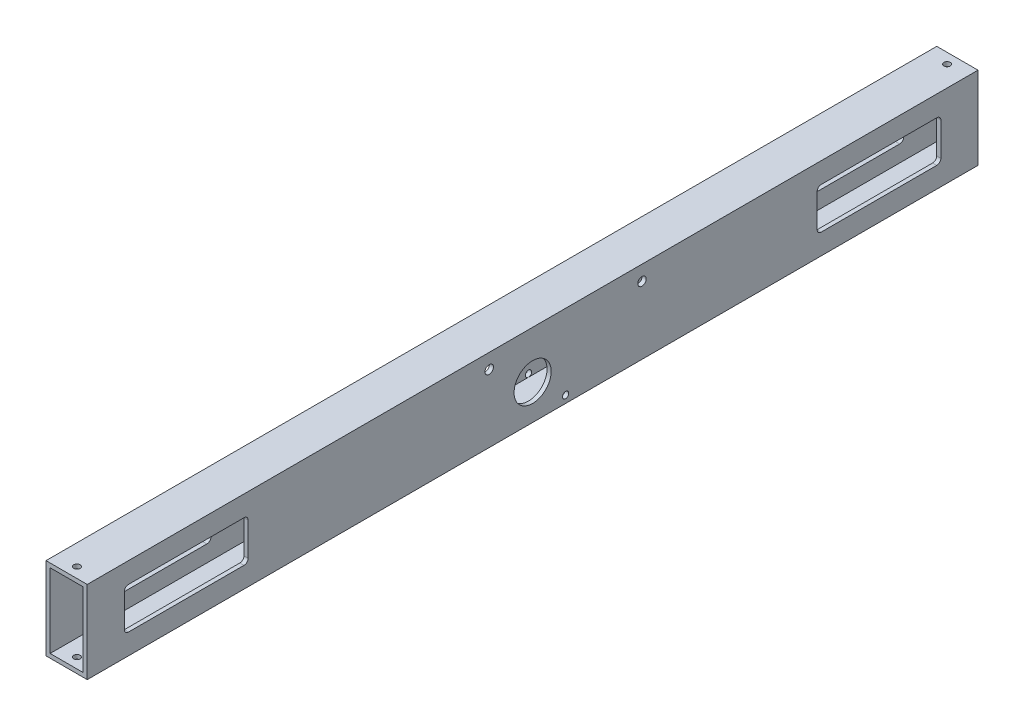
SolidWorks part; units mm, degrees
ref_plane "Front Plane" through (0, 0, 0) normal (0, 0, 1) x (1, 0, 0)
ref_plane "Top Plane" through (0, 0, 0) normal (0, 1, 0) x (1, 0, 0)
ref_plane "Right Plane" through (0, 0, 0) normal (1, 0, 0) x (0, 0, -1)
sketch "Sketch1" plane through (0, 0, 0) normal (0, 0, 1) x (1, 0, 0)
  line L1 (-12.1647, 2.5103) -> (19.5853, 2.5103)
  line L2 (-12.1647, 2.5103) -> (-12.1647, -60.9897)
  line L3 (-12.1647, -60.9897) -> (19.5853, -60.9897)
  line L4 (19.5853, 2.5103) -> (19.5853, -60.9897)
  line L5 (-8.9897, -0.6647) -> (16.4103, -0.6647)
  line L6 (-8.9897, -0.6647) -> (-8.9897, -57.8147)
  line L7 (-8.9897, -57.8147) -> (16.4103, -57.8147)
  line L8 (16.4103, -0.6647) -> (16.4103, -57.8147)
  dimension "D1" = 63.5
  dimension "D2" = 31.75
  dimension "D3" = 3.175
  dimension "D4" = 3.175
  dimension "D5" = 3.175
  dimension "D6" = 3.175
extrude "Boss-Extrude1" add sketch "Sketch1" along normal blind 685.8
sketch "Sketch3" plane through (-12.1647, 0, 0) normal (-1, 0, 0) x (0, 0, 1)
  line L0 (0, 2.5103) -> (0, -60.9897) construction
  line L1 (31.7754, -13.3647) -> (120.6754, -13.3647)
  line L2 (28.6004, -16.5397) -> (28.6004, -41.9397)
  line L3 (31.7754, -45.1147) -> (120.6754, -45.1147)
  line L4 (123.8504, -16.5397) -> (123.8504, -41.9397)
  line L5 (685.8, 2.5103) -> (0, 2.5103) construction
  line L6 (685.8, -60.9897) -> (0, -60.9897) construction
  line L7 (342.9, 2.5103) -> (342.9, -60.9897)
  line L8 (561.9496, -16.5397) -> (561.9496, -41.9397)
  line L9 (654.0246, -45.1147) -> (565.1246, -45.1147)
  line L10 (657.1996, -16.5397) -> (657.1996, -41.9397)
  line L11 (654.0246, -13.3647) -> (565.1246, -13.3647)
  arc A0 (28.6004, -41.9397) -> (31.7754, -45.1147) centre (31.7754, -41.9397) ccw
  arc A1 (120.6754, -45.1147) -> (123.8504, -41.9397) centre (120.6754, -41.9397) ccw
  arc A2 (120.6754, -13.3647) -> (123.8504, -16.5397) centre (120.6754, -16.5397) cw
  arc A3 (31.7754, -13.3647) -> (28.6004, -16.5397) centre (31.7754, -16.5397) ccw
  arc A4 (654.0246, -13.3647) -> (657.1996, -16.5397) centre (654.0246, -16.5397) cw
  arc A5 (565.1246, -13.3647) -> (561.9496, -16.5397) centre (565.1246, -16.5397) ccw
  arc A6 (565.1246, -45.1147) -> (561.9496, -41.9397) centre (565.1246, -41.9397) cw
  arc A7 (657.1996, -41.9397) -> (654.0246, -45.1147) centre (654.0246, -41.9397) cw
  dimension "D5" = 3.175
  dimension "D1" = 28.6004
  dimension "D2" = 15.875
  dimension "D3" = 15.875
  dimension "D4" = 95.25
extrude "Cut-Extrude1" cut sketch "Sketch3" against normal up to surface (31.75 mm away) contours L1 A3 L2 A0 L3 A1 L4 A2 | A7 L10 A4 L11 A5 L8 A6 L9 region at (-12.1647, -29.2397, 76.2254) region at (-12.1647, -29.2397, 609.5746) up to face at (19.5853, -29.2397, 342.9)
sketch "Sketch4" plane through (0, 2.5103, 0) normal (0, 1, 0) x (1, 0, 0)
  line L0 (19.5853, -685.8) -> (-12.1647, -685.8) construction
  line L1 (19.5853, 0) -> (-12.1647, 0) construction
  point P0 (3.7103, -677.8625)
  point P3 (3.7103, -685.8)
  point P4 (3.7103, -7.9375)
  dimension "D1" = 7.9375
  dimension "D2" = 7.9375
hole_wizard "#10 (0.1935) Diameter Hole1" positions "3DSketch1" profile "Sketch5" hole size "#10" standard "ANSI Inch" end condition through all
sketch3d "3DSketch1"
  point P0 (3.7103, 2.5103, 677.8625)
  point P3 (3.7103, 2.5103, 7.9375)
sketch "Sketch5" plane through (3.7103, 2.5103, 677.8625) normal (1, 0, 0) x (0, 0, 1)
  line L0 (0, 0) -> (0, 63.5)
  line L1 (0, 63.5) -> (2.4574, 63.5)
  line L2 (2.4574, 63.5) -> (2.4574, 0)
  line L5 (2.4574, 0) -> (0, 0)
  line L11 (0, -6.35) -> (0, 107.95) construction
  dimension "Thru Hole Dia." = 4.9149
  dimension "Thru Hole Depth" = 63.5
sketch "Sketch6" plane through (19.5853, 0, 0) normal (1, 0, 0) x (0, 0, -1)
  line L0 (-685.8, -60.9897) -> (0, -60.9897) construction
  line L4 (-685.8, -60.9897) -> (-685.8, 2.5103) construction
  circle A0 centre (-342.9, -34.0022) radius 14.2875
  circle A1 centre (-376.301, -8.9197) radius 3.2639
  circle A2 centre (-258.699, -8.9197) radius 3.2639
  circle A3 centre (-317.5, -55.4017) radius 2.413
  point P10 (-342.9, -60.9897)
  point P11 (-258.699, -8.9959)
  dimension "D1" = 28.575
  dimension "D4" = 6.5278
  dimension "D6" = 6.5278
  dimension "D8" = 4.826
  dimension "D2" = 26.9875
  dimension "D3" = 342.9
  dimension "D5" = 33.401
  dimension "D7" = 84.201
  dimension "D9" = 5.588
  dimension "D10" = 25.4
  dimension "D11" = 52.07
  dimension "D12" = 52.07
extrude "Cut-Extrude2" cut sketch "Sketch6" against normal up to surface (31.75 mm away) up to face at (-12.1647, -29.2397, 609.5746)
